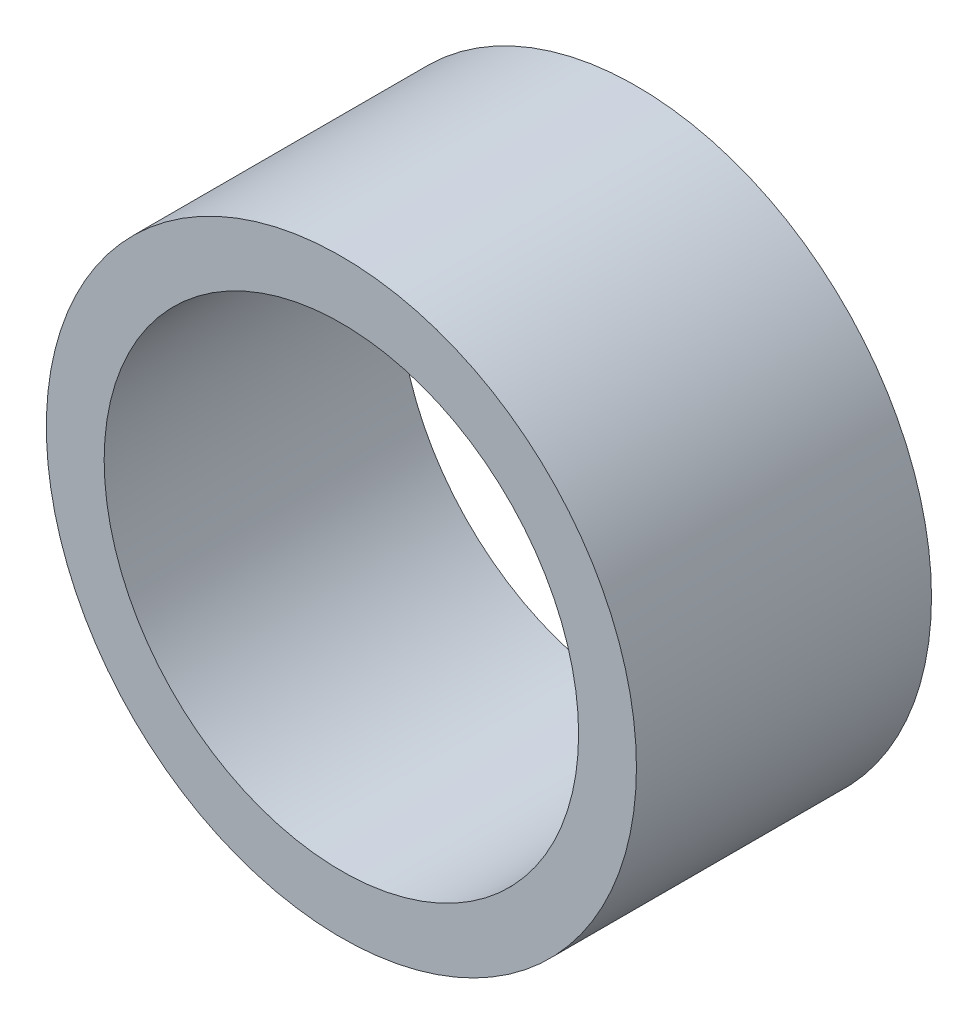
SolidWorks part; units mm, degrees
material "AISI 316 Stainless Steel Sheet (SS)"
ref_plane "Front Plane" through (0, 0, 0) normal (0, 0, 1) x (1, 0, 0)
ref_plane "Top Plane" through (0, 0, 0) normal (0, 1, 0) x (1, 0, 0)
ref_plane "Right Plane" through (0, 0, 0) normal (1, 0, 0) x (0, 0, -1)
sketch "Sketch1" plane through (0, 0, 0) normal (0, 0, 1) x (1, 0, 0)
  line L0 (6.35, 0) -> (-6.35, 0) construction
  line L1 (0, -5.1054) -> (0, 5.1054) construction
  line L2 (0, -6.35) -> (0, 6.35) construction
  circle A0 centre (0, 0) radius 6.35 construction
  circle A1 centre (0, 0) radius 5.1054 construction
  point P6 (0, 0)
  point P7 (-5.1054, 0)
  point P8 (5.1054, 0)
  point P10 (-6.35, 0)
  point P11 (6.35, 0)
  point P14 (0, 0)
  point P17 (0, 0)
  point P18 (0, 5.1054)
  point P19 (0, 6.35)
  point P20 (0, -5.1054)
  point P21 (0, -6.35)
  dimension "OD" = 12.7
  dimension "ID" = 10.2108
  dimension "Wall Thickness" = 1.2446
sketch "Sketch2" plane through (0, 0, 0) normal (1, 0, 0) x (0, 0, -1)
  line L0 (0, -5.1054) -> (0, 5.1054) construction
  line L1 (0, -5.1054) -> (0, 5.1054) construction
  line L2 (0, -6.35) -> (0, 6.35) construction
  line L3 (0, -6.35) -> (0, 6.35) construction
  line L4 (3.175, 6.35) -> (-3.175, 6.35) construction
  line L5 (3.175, 5.1054) -> (-3.175, 5.1054) construction
  line L6 (3.175, -5.1054) -> (-3.175, -5.1054) construction
  line L7 (3.175, -6.35) -> (-3.175, -6.35) construction
  line L8 (-3.175, -6.35) -> (-3.175, 6.35) construction
  line L9 (3.175, 6.35) -> (3.175, -6.35) construction
  line L10 (3.175, 0) -> (-3.175, 0) construction
  line L11 (2.4694, -6.35) -> (2.4694, 6.35) construction
  line L12 (-2.4694, -6.35) -> (-2.4694, 6.35) construction
  point P7 (0, 6.35)
  point P10 (0, 5.1054)
  point P13 (0, -5.1054)
  point P16 (0, -6.35)
  point P17 (-3.175, -6.35)
  point P18 (-3.175, -5.1054)
  point P19 (-3.175, 5.1054)
  point P20 (-3.175, 6.35)
  point P21 (3.175, 6.35)
  point P22 (3.175, 5.1054)
  point P23 (3.175, -5.1054)
  point P24 (3.175, -6.35)
  point P28 (0, 0)
  point P30 (2.4694, 0)
  point P31 (2.4694, -6.35)
  point P32 (2.4694, 6.35)
  point P35 (-2.4694, 0)
  point P36 (-2.4694, 6.35)
  point P37 (-2.4694, -6.35)
  dimension "Length" = 6.35
  dimension "Break Line" = 5.6444
sketch "Sketch3" plane through (0, 0, 0) normal (0, 0, 1) x (1, 0, 0)
  circle A0 centre (0, 0) radius 5.1054 construction
  circle A1 centre (0, 0) radius 6.35 construction
  circle A2 centre (0, 0) radius 5.1054
  circle A3 centre (0, 0) radius 6.35
extrude "Boss-Extrude1" add sketch "Sketch3" along normal up to vertex (3.175 mm away) and the other way up to vertex (3.175 mm away) up to point (0, 0, 3.175) other way up to point (0, 0, -3.175)
equation "\"Break Line@Sketch2\"=\"OD@Sketch1\"/2.25"
